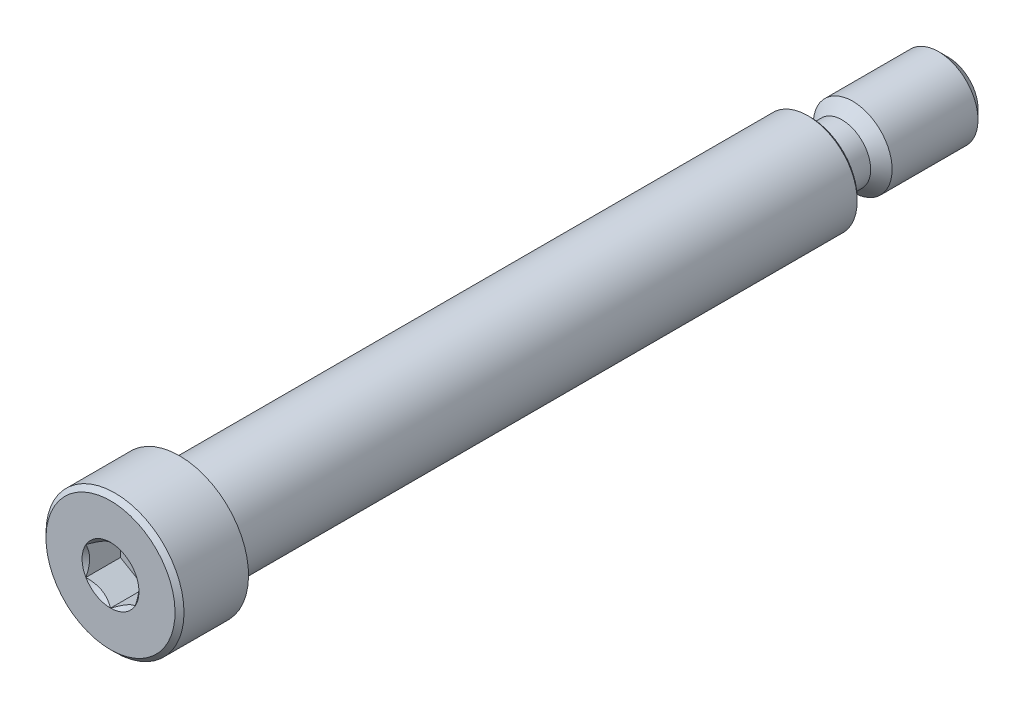
SolidWorks part; units mm, degrees
ref_plane "Front" through (0, 0, 0) normal (0, 0, 1) x (1, 0, 0)
ref_plane "Top" through (0, 0, 0) normal (0, 1, 0) x (1, 0, 0)
ref_plane "Right" through (0, 0, 0) normal (1, 0, 0) x (0, 0, -1)
sketch "Sketch1" plane through (0, 0, 0) normal (1, 0, 0) x (0, 0, -1)
  line L0 (0, 5.5562) -> (5.5562, 5.5562)
  line L1 (5.5562, 5.5562) -> (5.5562, 3.9687)
  line L2 (5.5562, 3.9687) -> (56.3562, 3.9687)
  line L3 (56.3562, 3.9687) -> (56.3562, 3.175)
  line L4 (56.3562, 3.175) -> (67.4688, 3.175)
  line L5 (67.4688, 3.175) -> (67.4687, 0)
  line L6 (67.4687, 0) -> (0, 0)
  line L7 (0, 0) -> (0, 5.5562)
  line L8 (0, 5.5562) -> (0, -5.5563) construction
  line L9 (67.4688, 3.175) -> (67.4687, -3.175) construction
  line L10 (56.3562, 3.9687) -> (56.3562, -3.9688) construction
  line L11 (67.4687, -3.175) -> (65.791, -3.175) construction
  line L12 (30.9563, 0) -> (30.9563, 3.9687) construction
  point P8 (65.5637, -3.175)
  point P12 (56.3562, 0)
  point P17 (10.6363, 3.9687)
  point P18 (30.9563, 0)
  point P19 (30.9563, 3.9687)
  point P20 (51.2762, 3.9687)
  point P21 (51.2762, -3.9688)
  point P22 (10.6363, -3.9688)
  dimension "Head Dia" = 11.1125
  dimension "Head Ht" = 5.5562
  dimension "Thread Lg" = 11.1125
  dimension "Thread Dia" = 6.35
  dimension "Shoulder Dia" = 7.9375
  dimension "Shoulder Lg" = 50.8
  dimension "D1" = 1.905
  dimension "D2" = 1.6778
  dimension "D3" = 25.4
  dimension "D4" = 5.08
revolve "Revolve1" add sketch "Sketch1" angle 360 mid plane about L6
ref_plane "Plane1" through (0, 0, -67.4687) normal (0, 0, 1) x (1, 0, 0)
sketch "Sketch3" [suppressed] plane through (0, 0, -67.4687) normal (0, 0, 1) x (1, 0, 0)
  circle A0 centre (0, 0) radius 3.175
sketch "Sketch5" plane through (0, 0, 0) normal (1, 0, 0) x (0, 0, -1)
  line L0 (56.3562, 3.9687) -> (60.5536, 3.9687)
  line L1 (60.5536, 3.9687) -> (58.8962, 2.3114)
  line L2 (58.8962, 2.3114) -> (57.2199, 2.3114)
  line L3 (56.3562, 3.9687) -> (56.3562, 3.175)
  line L5 (56.3562, 3.175) -> (67.4688, 3.175) construction
  line L6 (67.4687, 0) -> (58.8962, 0) construction
  line L7 (63.1825, 0) -> (63.1825, -3.175) construction
  arc A0 (56.3562, 3.175) -> (57.2199, 2.3114) centre (57.2199, 3.175) ccw
  dimension "D1" = 45
  dimension "CADB" = 2.54
  dimension "CADA" = 4.6228
revolve "Cut-Revolve1" cut sketch "Sketch5" angle 360 mid plane about L6
chamfer "Chamfer1" distance 0.7937 angle 45 1 edges at (0, 3.175, -67.4688)
chamfer "Chamfer2" distance 0.3612 angle 45 1 edges at (0, 5.5562, 0)
chamfer "Chamfer3" distance 0.2032 angle 45 1 edges at (0, 3.9687, -56.3562)
sketch "Sketch10" plane through (0, 0, 0) normal (1, 0, 0) x (0, 0, -1)
  line L0 (0.3612, 0) -> (5.1951, 0) construction
  line L1 (0.3612, -5.5562) -> (0.3612, 5.5562) construction
  line L3 (0.3612, 0) -> (0, 0) construction
  line L4 (5.1951, 0) -> (5.5562, 0) construction
  line L5 (5.5562, -5.5562) -> (5.5563, 5.5562) construction
  point P6 (2.7781, 0)
  dimension "D1" = 4.8339
ref_plane "Plane2" through (0, 0, -2.7781) normal (0, 0, 1) x (1, 0, 0)
sketch "Sketch11" plane through (0, 0, -2.7781) normal (0, 0, 1) x (1, 0, 0)
  line L0 (0, 5.2673) -> (0, 5.5562) construction
  line L1 (0, 5.2673) -> (0.1668, 5.5562)
  line L2 (0, 5.2673) -> (-0.1668, 5.5562)
  line L3 (-0.1668, 5.5562) -> (0.1668, 5.5562)
  line L4 (0, 0) -> (-0.1668, 5.5562) construction
  line L5 (0.1668, 5.5562) -> (0, 0) construction
  circle A1 centre (0, 0) radius 5.5562 construction
  circle A2 centre (0, 0) radius 5.2673 construction
  circle A3 centre (0, 0) radius 5.1951 construction
  point P3 (0, 0.0018)
  point P8 (2.3908, 0.7309)
  dimension "D1" = 0.2889
  dimension "D2" = 3.439
extrude "Cut-Extrude5" [suppressed] cut sketch "Sketch11" against normal mid plane 4.5922
pattern_circular "CirPattern1" [suppressed] count 99 over 360 of bodies 119
sketch "Sketch8" plane through (0, 0, 0) normal (0, 0, 1) x (1, 0, 0)
  line L1 (1.9844, 1.1457) -> (0, 2.2914)
  line L2 (0, 2.2914) -> (-1.9844, 1.1457)
  line L3 (-1.9844, 1.1457) -> (-1.9844, -1.1457)
  line L4 (-1.9844, -1.1457) -> (0, -2.2914)
  line L5 (0, -2.2914) -> (1.9844, -1.1457)
  line L6 (1.9844, -1.1457) -> (1.9844, 1.1457)
  circle A0 centre (0, 0) radius 1.9844 construction
  dimension "Hex" = 3.9688
extrude "Cut-Extrude2" cut sketch "Sketch8" against normal blind 2.7781
sketch "Sketch9" plane through (0, 0, 0) normal (0, 0, 1) x (1, 0, 0)
  circle A0 centre (0, 0) radius 2.2914
extrude "Cut-Extrude4" cut sketch "Sketch9" against normal blind 2.7781 draft 45
sketch "Front Sketch" plane through (0, 0, 0) normal (0, 0, 1) x (1, 0, 0)
  line L0 (1.9844, -1.1457) -> (1.9844, 1.1457) construction
  line L1 (-1.9844, 1.1457) -> (-1.9844, -1.1457) construction
  circle A0 centre (0, 0) radius 5.5562 construction
  point P4 (-1.9844, 0)
  point P5 (1.9844, 0)
  point P6 (5.5562, 0)
  point P9 (-5.5562, 0)
ref_plane "Contact Plane 1" through (0, 0, -5.5562) normal (0, 0, -1) x (-1, 0, 0)
ref_axis "Center Axis 1" through (0, 0, -67.4687) along (0, 0, 1)
curve "Helix/Spiral1" [suppressed] pitch 1.27 height 12.3825 turns 9.75
sketch "Sketch4" [suppressed] plane through (0, 0, 0) normal (1, 0, 0) x (0, 0, -1)
  line L0 (67.3894, 3.3125) -> (68.6594, 3.3125) construction
  line L1 (68.6594, 3.3125) -> (68.0244, 2.2126) construction
  line L3 (68.0244, 2.2126) -> (67.3894, 3.3125) construction
  line L4 (67.4291, 3.2437) -> (68.6197, 3.2437) construction
  line L5 (67.4688, 3.175) -> (68.58, 3.175) construction
  line L6 (67.945, 2.3501) -> (68.1037, 2.3501) construction
  line L7 (68.0244, 2.3501) -> (68.0244, 2.2126) construction
  line L8 (68.0244, 3.3125) -> (68.0244, 3.175) construction
  line L9 (67.4291, 3.2437) -> (68.6197, 3.2437)
  line L10 (68.6197, 3.2437) -> (68.1037, 2.3501)
  line L11 (68.1037, 2.3501) -> (67.945, 2.3501)
  line L12 (67.945, 2.3501) -> (67.4291, 3.2437)
  point P14 (68.0244, 3.2437)
  point P15 (68.0244, 3.3125)
  dimension "D1" = 1.27
  dimension "D2" = 0.1588
sweep "Cut-Sweep1" [suppressed] cut profiles "Sketch4" path "Helix/Spiral1"
sketch "Sketch12" [suppressed] plane through (0, 0, 0) normal (1, 0, 0) x (0, 0, -1)
  line L1 (56.3562, 3.7655) -> (56.1531, 3.9687)
  line L2 (56.1531, 3.9687) -> (5.5562, 3.9687)
  line L3 (5.5562, 3.9687) -> (5.5562, 0)
  line L4 (5.5562, -5.5562) -> (5.5563, 5.5562) construction
  line L5 (5.5562, 0) -> (56.3562, 0)
  line L6 (56.3562, 3.7655) -> (56.3562, 3.175)
  line L7 (58.8962, 2.3114) -> (57.2199, 2.3114) construction
  line L8 (58.8962, 2.3114) -> (57.2199, 2.3114)
  line L9 (58.8962, 2.3114) -> (58.8962, 0)
  line L10 (58.8962, 0) -> (56.3562, 0)
  arc A0 (56.3562, 3.175) -> (57.2199, 2.3114) centre (57.2199, 3.175) ccw construction
  arc A1 (56.3562, 3.175) -> (57.2199, 2.3114) centre (57.2199, 3.175) ccw
revolve "Revolve2" [suppressed] add sketch "Sketch12" angle 360 about L5
equation "\"D3@Helix/Spiral1\" = \"Thread Lg@Sketch1\" + \"D4@Helix/Spiral1\""
equation "\"D1@Chamfer1\" = \"Thread Dia@Sketch1\" * .125"
equation "\"D1@Cut-Extrude2\"= \"Head Ht@Sketch1\" * .5"
equation "\"D1@Cut-Extrude4\" = \"D1@Cut-Extrude2\""
equation "\"D1@Chamfer2\" = \"Head Dia@Sketch1\" * .0325"
equation "\"D1@Sketch1\"=\"D4@Helix/Spiral1\"*1.5"
equation "\"D1@Sketch11\"=\"D1@Chamfer2\"*.8"
equation "\"D1@Cut-Extrude5\"=\"D1@Sketch10\"*.95"
equation "\"D1@CirPattern1\"=(360/\"D2@Sketch11\")-6"
equation "\"D3@Sketch1\"=\"Shoulder Lg@Sketch1\"/2"
equation "\"D4@Sketch1\"=\"D3@Sketch1\"*.2"
equation "\"D1@Sketch4\"=\"D4@Helix/Spiral1\""
equation "\"D2@Sketch4\"=\"D1@Sketch4\"/8"
